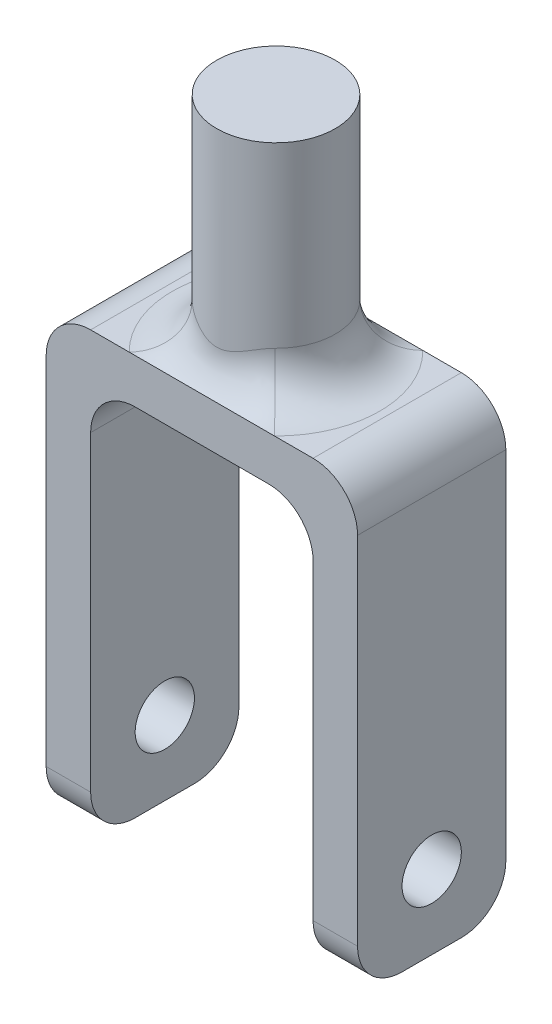
SolidWorks part; units mm, degrees
ref_plane "前视基准面" through (0, 0, 0) normal (0, 0, 1) x (1, 0, 0)
ref_plane "上视基准面" through (0, 0, 0) normal (0, 1, 0) x (1, 0, 0)
ref_plane "右视基准面" through (0, 0, 0) normal (1, 0, 0) x (0, 0, -1)
sketch "草图1" plane through (0, 0, 0) normal (0, 1, 0) x (1, 0, 0)
  line L1 (21, 10) -> (-21, 10)
  line L2 (21, 10) -> (21, -10)
  line L3 (21, -10) -> (-21, -10)
  line L4 (-21, 10) -> (-21, -10)
  line L5 (21, 10) -> (-21, -10) construction
  line L6 (21, -10) -> (-21, 10) construction
  point P0 (0, 0)
extrude "凸台-拉伸1" add sketch "草图1" against normal blind 60
sketch "草图2" plane through (0, 0, 0) normal (0, 1, 0) x (1, 0, 0)
  circle A0 centre (0, 0) radius 8
extrude "凸台-拉伸2" add sketch "草图2" along normal blind 30
sketch "草图3" plane through (0, 0, 10) normal (0, 0, 1) x (1, 0, 0)
  line L0 (-21, -60) -> (21, -60) construction
  line L1 (-15, -60) -> (15, -60)
  line L2 (-15, -60) -> (-15, -6)
  line L3 (-15, -6) -> (15, -6)
  line L4 (15, -60) -> (15, -6)
extrude "切除-拉伸1" cut sketch "草图3" against normal through all
fillet "圆角1" radius 6 9 edges at (-21, 0, 0) (21, 0, 0) (15, -6, 0) (-15, -6, 0) (-18, -60, -10) (18, -60, -10) (-18, -60, 10) (18, -60, 10) (0, 0, 8)
sketch "草图4" plane through (21, 0, 0) normal (1, 0, 0) x (0, 0, -1)
  circle A0 centre (0, -50) radius 4
extrude "切除-拉伸2" cut sketch "草图4" against normal through all
